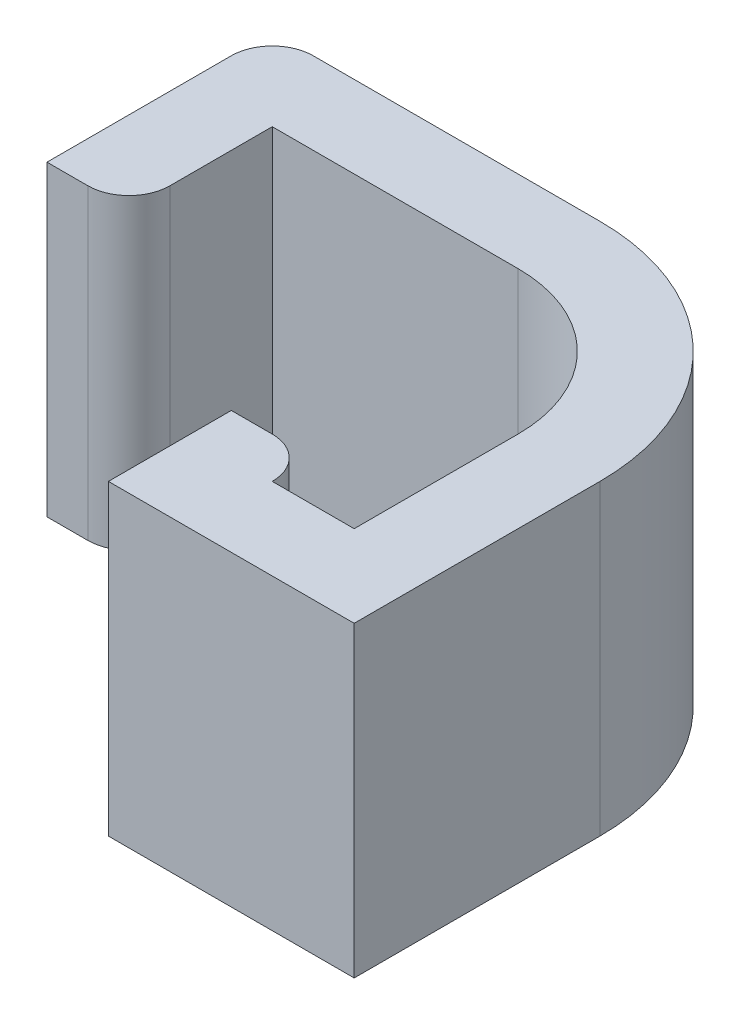
SolidWorks part; units mm, degrees
material "6061-T6 (SS)"
ref_plane "Front Plane" through (0, 0, 0) normal (0, 0, 1) x (1, 0, 0)
ref_plane "Top Plane" through (0, 0, 0) normal (0, 1, 0) x (1, 0, 0)
ref_plane "Right Plane" through (0, 0, 0) normal (1, 0, 0) x (0, 0, -1)
ref_axis "Axis1" through (0, 0, 55) along (0, 0, -1)
sketch "Sketch1" plane through (0, 0, 0) normal (0, 1, 0) x (1, 0, 0)
  line L0 (0, 0) -> (0, 7)
  line L1 (0, 7) -> (12, 7)
  line L2 (19, 0) -> (19, -8)
  line L3 (19, -8) -> (15, -8)
  line L4 (15, -8) -> (15, -6)
  line L5 (-4, 0) -> (-4, 11)
  line L6 (-4, 11) -> (12, 11)
  line L7 (23, 0) -> (23, -12)
  line L8 (23, -12) -> (11, -12)
  line L9 (11, -12) -> (11, -6)
  line L10 (0, 0) -> (-4, 0)
  line L11 (15, -6) -> (11, -6)
  arc A0 (12, 7) -> (19, 0) centre (12, 0) cw
  arc A1 (12, 11) -> (23, 0) centre (12, 0) cw
  dimension "D1" = 7
  dimension "D2" = 19
  dimension "D3" = 7
  dimension "D4" = 4
  dimension "D5" = 2
  dimension "D6" = 8
  dimension "D7" = 4
extrude "Boss-Extrude1" add sketch "Sketch1" along normal blind 15
fillet "Fillet1" radius 2 3 edges at (15, 7.5, 6) (0, 7.5, 0) (-4, 7.5, -11)
